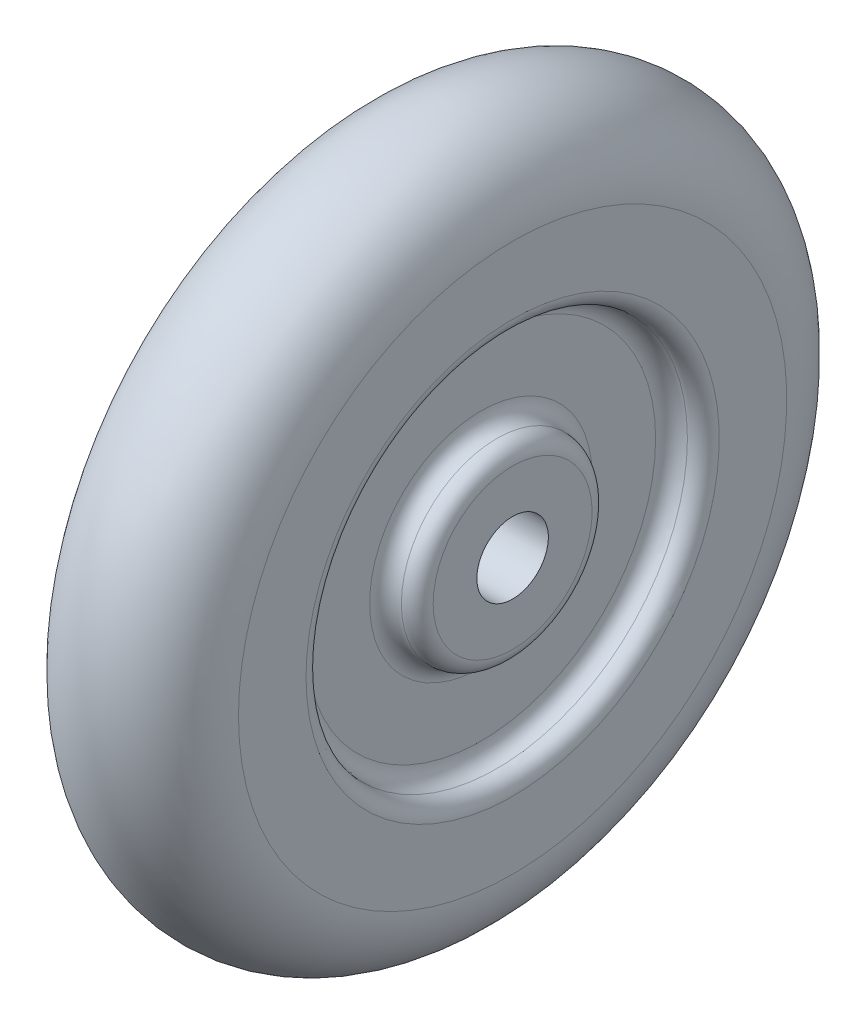
SolidWorks part; units mm, degrees
ref_plane "Front Plane" through (0, 0, 0) normal (0, 0, 1) x (1, 0, 0)
ref_plane "Top Plane" through (0, 0, 0) normal (0, 1, 0) x (1, 0, 0)
ref_plane "Right Plane" through (0, 0, 0) normal (1, 0, 0) x (0, 0, -1)
sketch "Sketch1" plane through (0, 0, 0) normal (0, 0, 1) x (1, 0, 0)
  line L0 (-11.2518, -0.83) -> (9.0638, -0.83) construction
  line L2 (-5, 16.42) -> (-5, 1.42)
  line L3 (-5, 1.42) -> (5, 1.42)
  line L4 (5, 16.42) -> (5, 1.42)
  arc A1 (5, 16.42) -> (-5, 16.42) centre (0, 16.42) ccw
  point P5 (0, 21.42)
  dimension "D1" = 5
  dimension "D2" = 20
  dimension "D3" = 2.25
revolve "Revolve1" add sketch "Sketch1" angle 360 about L0
sketch "Sketch4" plane through (5, 0, 0) normal (1, 0, 0) x (0, 0, -1)
  circle A0 centre (0, -0.83) radius 12
  circle A1 centre (0, -0.83) radius 6
extrude "Cut-Extrude2" cut sketch "Sketch4" against normal blind 2
fillet "Fillet1" radius 1 4 edges at (3, -0.83, -6) (5, -0.83, -6) (5, -0.83, -12) (3, -0.83, -12)
mirror "Mirror2" about plane through (0, 0, 0) normal (1, 0, 0) of "Cut-Extrude2"
fillet "Fillet2" radius 1 4 edges at (-5, -0.83, -12) (-3, -0.83, -12) (-3, -0.83, -6) (-5, -0.83, -6)
